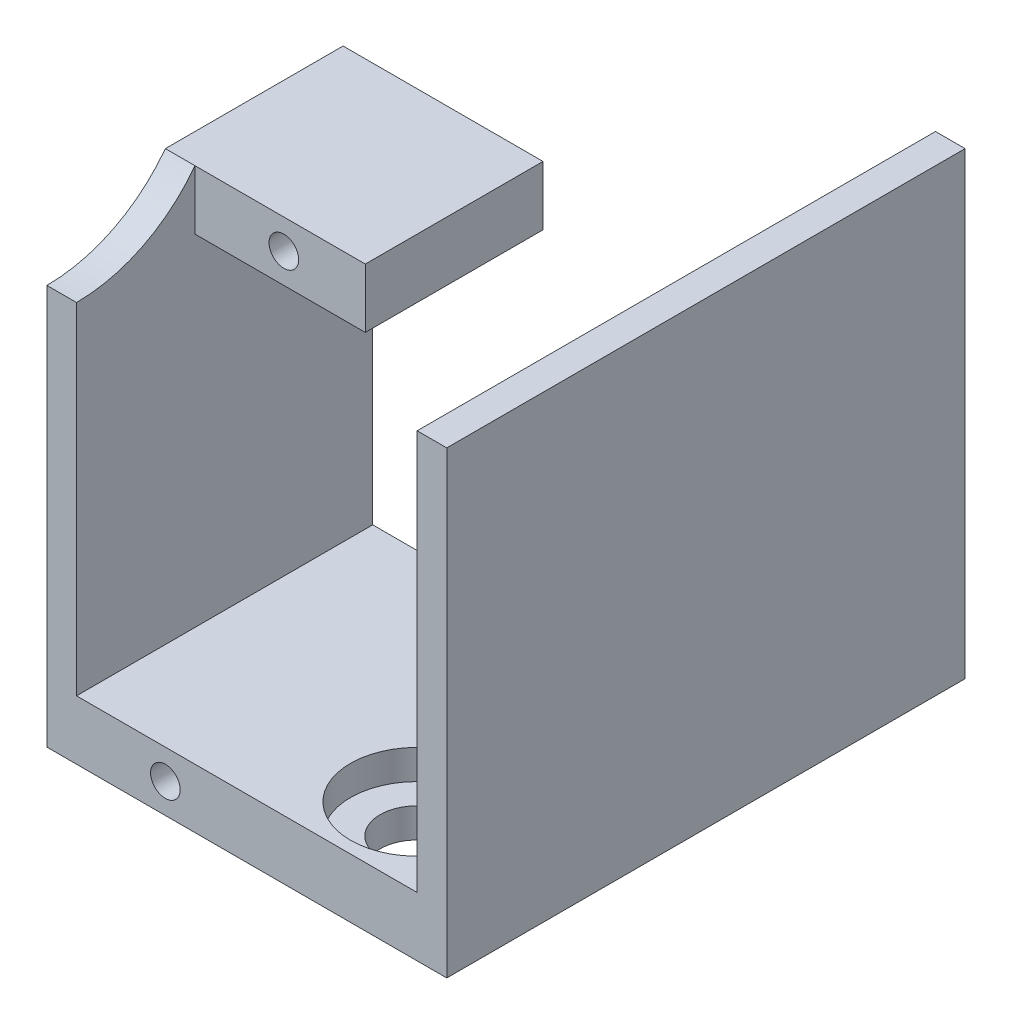
SolidWorks part; units mm, degrees
ref_plane "Front Plane" through (0, 0, 0) normal (0, 0, 1) x (1, 0, 0)
ref_plane "Top Plane" through (0, 0, 0) normal (0, 1, 0) x (1, 0, 0)
ref_plane "Right Plane" through (0, 0, 0) normal (1, 0, 0) x (0, 0, -1)
sketch "Sketch1" plane through (0, 0, 0) normal (0, 1, 0) x (1, 0, 0)
  line L0 (0, 10) -> (0, -10) construction
  line L1 (10, -10) -> (-10, -10)
  line L2 (10, -10) -> (10, 10)
  line L3 (10, 10) -> (-10, 10)
  line L4 (-10, -10) -> (-10, 10)
  line L5 (10, -10) -> (-10, 10) construction
  line L6 (10, 10) -> (-10, -10) construction
  circle A0 centre (-4.6967, 4.6967) radius 2.5 construction
  circle A1 centre (4.6967, -4.6967) radius 2.5
  circle A2 centre (4.6967, 4.6967) radius 2.5
  circle A3 centre (-4.6967, -4.6967) radius 2.5 construction
  point P0 (0, 0)
  dimension "D2" = 5
  dimension "D1" = 20
  dimension "D3" = 7.5
extrude "Boss-Extrude1" add sketch "Sketch1" along normal blind 2
sketch "Sketch2" plane through (0, 2, 0) normal (0, 1, 0) x (1, 0, 0)
  line L1 (10, 10) -> (60.8404, 10)
  line L2 (10, 10) -> (10, -10)
  line L3 (10, -10) -> (60.8404, -10)
  line L4 (-10, 10) -> (-10, -10)
  line L5 (-10, -10) -> (10, -10)
  line L6 (10, -10) -> (10, 10)
  line L7 (10, 10) -> (-10, 10)
  line L8 (-10, 10) -> (-10, -10)
  line L9 (-10, -10) -> (10, -10)
  line L10 (10, -10) -> (10, 10)
  line L11 (10, 10) -> (-10, 10)
  line L12 (60.8404, 10) -> (60.8404, -10)
  circle A1 centre (4.6967, -4.6967) radius 2.5 construction
  circle A5 centre (4.6967, -4.6967) radius 2.5
  circle A11 centre (4.6967, -4.6967) radius 4.5
  circle A12 centre (4.6967, 4.6967) radius 2.5 construction
  circle A13 centre (4.6967, 4.6967) radius 2.5
  circle A14 centre (4.6967, 4.6967) radius 4.5
  dimension "D2" = 9
  dimension "D4" = 50.8404
  dimension "D1" = 0
extrude "Boss-Extrude2" add sketch "Sketch2" along normal blind 2
sketch "Sketch6" plane through (0, 4, 0) normal (0, 1, 0) x (1, 0, 0)
  line L0 (-10, 10) -> (-10, -10) construction
  line L1 (-10, -10) -> (-13, -10)
  line L2 (-10, -10) -> (-10, 10)
  line L3 (-10, 10) -> (-13, 10)
  line L4 (-13, -10) -> (-13, 10)
  line L7 (10, 10) -> (-10, 10) construction
  point P0 (-10, 0)
  point P9 (-3.3737, 10)
  point P10 (-10, 10)
  point P11 (-7.2294, 10)
  dimension "D1" = 3
extrude "Boss-Extrude4" add sketch "Sketch6" against normal up to surface (4 mm away) up to face at (0, 0, 0)
sketch "Sketch4" plane through (-13, 0, 0) normal (-1, 0, 0) x (0, 0, 1)
  line L1 (-10, 0) -> (10, 0)
  line L2 (-10, 0) -> (-10, 27)
  line L3 (-10, 27) -> (10, 27)
  line L4 (10, 0) -> (10, 27)
  line L5 (10, 0) -> (10, 4) construction
  point P7 (-9.1372, 0.8714)
  dimension "D1" = 27
extrude "Boss-Extrude3" add sketch "Sketch4" along normal blind 2
sketch "Sketch5" plane through (0, 0, -10) normal (0, 0, -1) x (-1, 0, 0)
  line L0 (13, 4) -> (7, 4) construction
  line L1 (13, 27) -> (13, 4) construction
  line L2 (-10, 4) -> (13, 4) construction
  line L3 (7, 4) -> (7, 0) construction
  line L4 (-10, 0) -> (15, 0) construction
  circle A0 centre (7, 2) radius 1
  dimension "D2" = 2
  dimension "D1" = 6
extrude "Cut-Extrude1" cut sketch "Sketch5" against normal up to surface (20 mm away) contours A0 up to face at (-6, 10.3333, 10)
sketch "Sketch7" plane through (0, 27, 0) normal (0, 1, 0) x (1, 0, 0)
  line L0 (10, 10) -> (-13, 10) construction
  line L1 (-15, 10) -> (-1.5, 10)
  line L2 (-15, 10) -> (-15, -2)
  line L3 (-15, -2) -> (-1.5, -2)
  line L4 (-1.5, 10) -> (-1.5, -2)
  point P5 (-4.7903, -2)
  point P8 (-1.5, 10)
  dimension "D1" = 12
extrude "Boss-Extrude5" add sketch "Sketch7" along normal blind 4
ref_plane "Plane1" through (0, 15.5, 0) normal (0, 1, 0) x (1, 0, 0)
mirror "Mirror1" about plane through (0, 15.5, 0) normal (0, 1, 0) of "Cut-Extrude1"
fillet "Fillet3" radius 10 1 edges at (-14, 27, 2)
sketch "Sketch9" plane through (10, 0, 0) normal (1, 0, 0) x (0, 0, -1)
  line L0 (-2, 31) -> (10, 31) construction
  line L5 (-10, 0) -> (25, 0)
  line L6 (-10, 0) -> (-10, 31)
  line L7 (-10, 31) -> (25, 31)
  line L8 (25, 0) -> (25, 31)
  line L9 (10, 27) -> (10, 4) construction
  dimension "D1" = 15
extrude "Boss-Extrude6" add sketch "Sketch9" along normal blind 2
